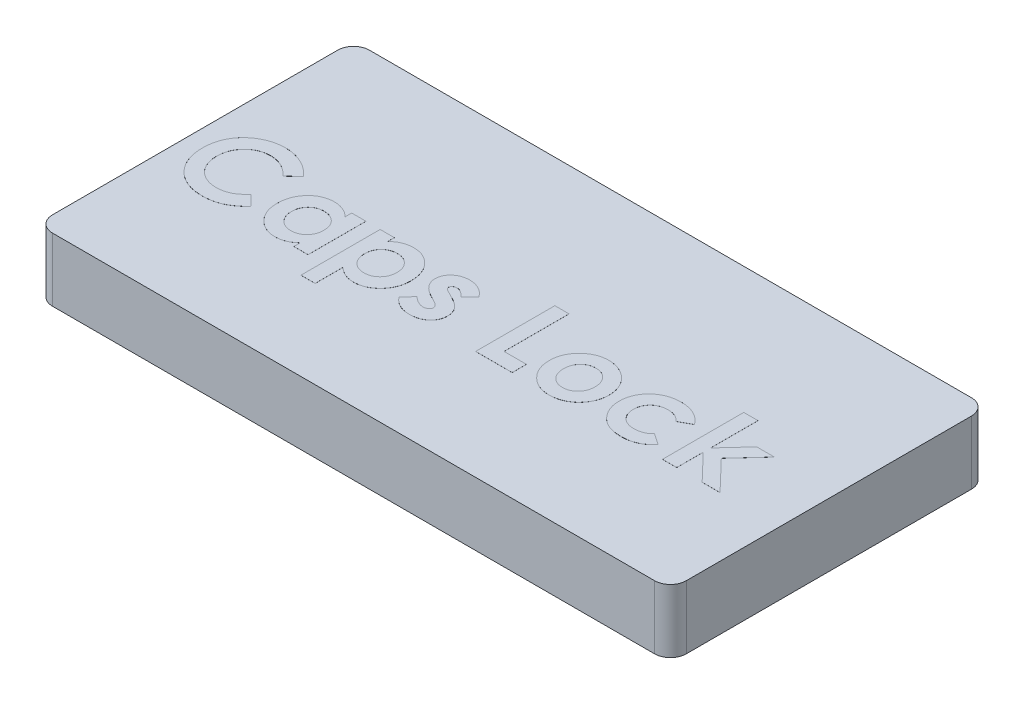
SolidWorks part; units mm, degrees
ref_plane "Front Plane" through (0, 0, 0) normal (0, 0, 1) x (1, 0, 0)
ref_plane "Top Plane" through (0, 0, 0) normal (0, 1, 0) x (1, 0, 0)
ref_plane "Right Plane" through (0, 0, 0) normal (1, 0, 0) x (0, 0, -1)
sketch "Sketch1" plane through (0, 0, 0) normal (0, 1, 0) x (1, 0, 0)
  line L0 (0, 0) -> (25.4, 0)
  line L1 (25.4, 0) -> (25.4, 12.7)
  line L2 (25.4, 12.7) -> (0, 12.7)
  line L3 (0, 12.7) -> (0, 0)
  dimension "D1" = 25.4
  dimension "D2" = 12.7
extrude "Boss-Extrude1" add sketch "Sketch1" along normal blind 2.54
fillet "Fillet1" radius 0.635 4 edges at (0, 1.27, -12.7) (25.4, 1.27, -12.7) (25.4, 1.27, 0) (0, 1.27, 0)
shell "Shell1" thickness 0.635 removed face at (12.7, 0, -6.35)
sketch "Sketch2" plane through (0, 1.905, 0) normal (0, -1, 0) x (-1, 0, 0)
  line L0 (-0.635, 6.35) -> (-24.765, 6.35) construction
  line L1 (-0.635, 12.065) -> (-0.635, 0.635) construction
  line L2 (-24.765, 0.635) -> (-24.765, 12.065) construction
  line L3 (-12.7, 0.635) -> (-12.7, 12.065) construction
  line L4 (-0.635, 0.635) -> (-24.765, 0.635) construction
  line L5 (-24.765, 12.065) -> (-0.635, 12.065) construction
  circle A0 centre (-12.7, 6.35) radius 2.54
  dimension "D1" = 5.08
extrude "Boss-Extrude2" add sketch "Sketch2" along normal up to surface (1.905 mm away) up to face at (12.7, 0, -6.35)
sketch "Sketch3" plane through (0, 2.54, 0) normal (0, 1, 0) x (1, 0, 0)
  line L0 (0.635, 0) -> (24.765, 0) construction
  line L1 (0, 12.065) -> (0, 0.635) construction
  text T0 "<b>Caps Lock</b>"
  dimension "D1" = 4.3688
  dimension "D2" = 0.4826
extrude "Boss-Extrude3" add sketch "Sketch3" along normal blind 0.0025
